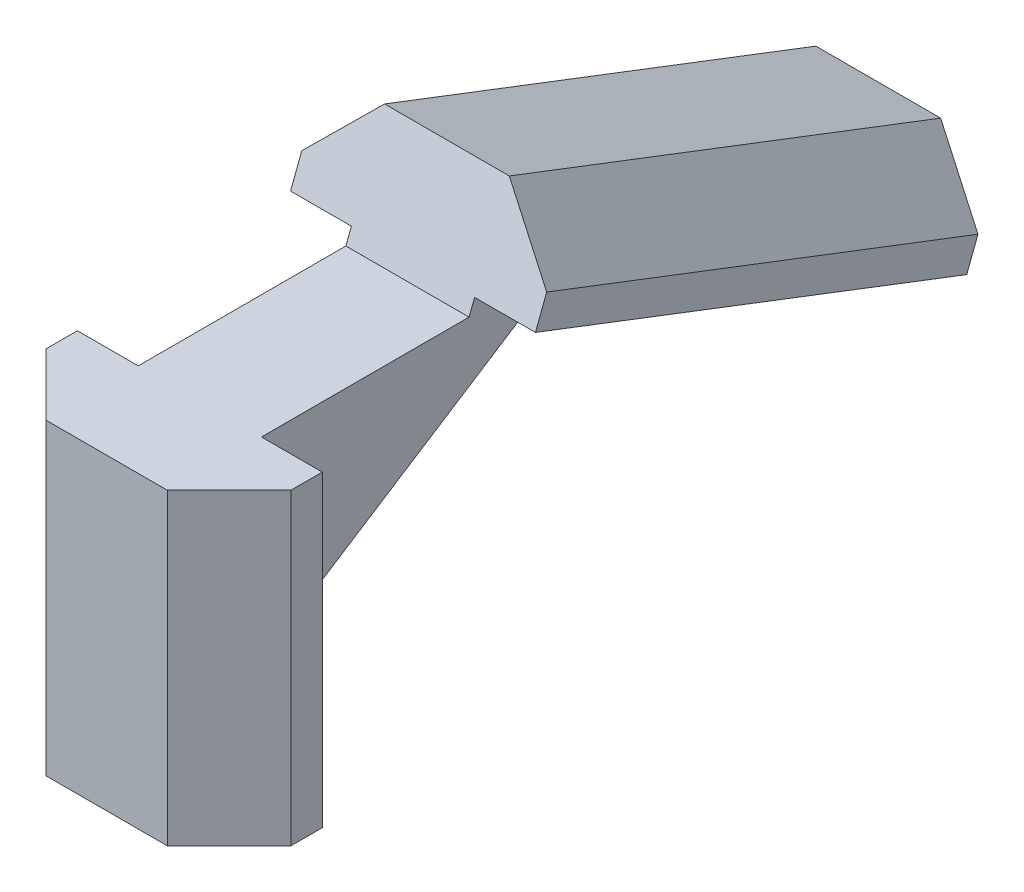
SolidWorks part; units mm, degrees
ref_plane "Front Plane" through (0, 0, 0) normal (0, 0, 1) x (1, 0, 0)
ref_plane "Top Plane" through (0, 0, 0) normal (0, 1, 0) x (1, 0, 0)
ref_plane "Right Plane" through (0, 0, 0) normal (1, 0, 0) x (0, 0, -1)
sketch "Sketch1" plane through (0, 0, 0) normal (0, 1, 0) x (1, 0, 0)
  line L0 (-3.9407, -6.0493) -> (3.9407, -6.0493)
  line L1 (7.95, 0) -> (7.95, -2.04)
  line L2 (7.95, -2.04) -> (3.9407, -6.0493)
  line L4 (0, 0) -> (0, 4.5954) construction
  line L5 (-7.95, -2.04) -> (-3.9407, -6.0493)
  line L6 (-7.95, 0) -> (-7.95, -2.04)
  line L7 (-7.95, 0) -> (7.95, 0)
  dimension "D1" = 15.9
  dimension "D2" = 2.04
  dimension "D3" = 5.67
extrude "Boss-Extrude1" add sketch "Sketch1" against normal blind 20 contours L7 L1 L2 L0 L5 L6
ref_plane "Plane1" through (0, 0, 0) normal (1, 0, 0) x (0, 0, -1)
sketch "Sketch2" plane through (0, 0, 0) normal (1, 0, 0) x (0, 0, -1)
  line L1 (0, -20) -> (0, 0) construction
  line L10 (5.1098, 0) -> (23.7814, -7.1674)
  line L12 (5.1098, 0) -> (6.1849, 2.8007)
  line L13 (6.1849, 2.8007) -> (24.8565, -4.3666)
  line L14 (24.8565, -4.3666) -> (23.7814, -7.1674)
  dimension "D1" = 69
  dimension "D2" = 3
  dimension "D3" = 20
  dimension "D4" = 5.1098
sketch "Sketch4" plane through (0, 0, 0) normal (1, 0, 0) x (0, 0, -1)
  line L0 (0, 0) -> (13.4811, 0)
  line L1 (6.1849, 2.8007) -> (24.8565, -4.3666) construction
  line L2 (13.4811, 0) -> (17.2781, -1.4575)
  line L3 (17.2781, -1.4575) -> (0, -12.5397)
  line L4 (0, -20) -> (0, 0) construction
  line L5 (0, -12.5397) -> (0, 0)
extrude "Boss-Extrude3" add sketch "Sketch4" along normal mid plane 8 contours L5 L0 L2 L3
ref_plane "Plane2" through (0, 5.4439, -2.0897) normal (0, 0.9336, -0.3584) x (1, 0, 0)
sketch "Sketch6" plane through (0, 5.4439, -2.0897) normal (0, 0.9336, -0.3584) x (1, 0, 0)
  line L0 (-4, 16.6528) -> (4, 16.6528)
  line L1 (4, 16.6528) -> (4, 12.5857)
  line L2 (4, 12.5857) -> (-4, 12.5857)
  line L3 (-4, 12.5857) -> (-4, 16.6528)
extrude "Boss-Extrude4" add sketch "Sketch6" against normal up to surface (1 mm away) contours L3 L0 L1 L2 up to face at (0, -0.7288, -15.3796)
ref_plane "Plane3" through (0, -4.5103, -11.7497) normal (0, 0.3584, 0.9336) x (1, 0, 0)
sketch "Sketch8" plane through (0, -4.5103, -11.7497) normal (0, 0.3584, 0.9336) x (1, 0, 0)
  line L0 (-4.05, 11.9869) -> (4.05, 11.9869)
  line L1 (55, 5.8312) -> (-55, 5.8312) construction
  line L2 (7.95, 5.8312) -> (7.95, 7.8712)
  line L3 (7.95, 7.8712) -> (4.05, 11.9869)
  line L4 (-7.95, 5.8312) -> (-7.95, 7.8712)
  line L5 (0, 5.8312) -> (0, 14.4021) construction
  line L6 (-7.95, 7.8712) -> (-4.05, 11.9869)
  line L7 (7.95, 5.8312) -> (-7.95, 5.8312)
  dimension "D1" = 15.9
  dimension "D2" = 5.67
  dimension "D3" = 2.04
  dimension "D4" = 8.1
extrude "Boss-Extrude5" add sketch "Sketch8" against normal blind 30 contours L7 L4 L6 L0 L3 L2
